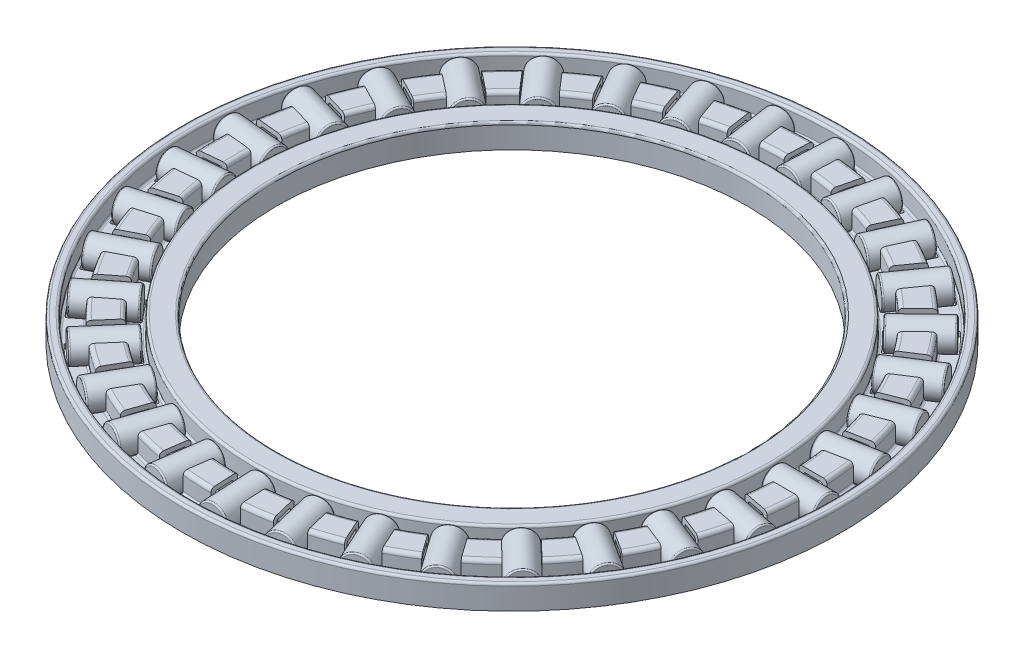
SolidWorks part; units mm, degrees
ref_plane "Front Plane" through (0, 0, 0) normal (0, 0, 1) x (1, 0, 0)
ref_plane "Top Plane" through (0, 0, 0) normal (0, 1, 0) x (1, 0, 0)
ref_plane "Right Plane" through (0, 0, 0) normal (1, 0, 0) x (0, 0, -1)
sketch "Sketch1" plane through (0, 0, 0) normal (1, 0, 0) x (0, 0, -1)
  line L0 (-35, 0) -> (35, 0) construction
  line L1 (-25.025, 0) -> (25.025, 0) construction
  line L2 (35, -1.5) -> (35, 1.5) construction
  line L3 (25.025, -1.275) -> (25.025, 1.275) construction
  line L4 (25.025, -1.275) -> (25.85, -1.275) construction
  line L5 (25.85, -1.275) -> (25.85, 0.7792) construction
  line L6 (25.85, 0.7792) -> (26.675, 0.7792) construction
  line L7 (26.675, 0.7792) -> (26.675, -1.275) construction
  line L8 (26.675, -1.275) -> (29.5042, -1.275) construction
  line L9 (29.5042, -1.275) -> (29.5042, 0.7792) construction
  line L10 (29.5042, 0.7792) -> (31.5042, 0.7792) construction
  line L11 (31.5042, 0.7792) -> (31.5042, -1.275) construction
  line L12 (31.5042, -1.275) -> (34.3333, -1.275) construction
  line L13 (34.3333, -1.275) -> (34.3333, 0.7792) construction
  line L14 (34.3333, 0.7792) -> (34.6667, 0.7792) construction
  line L15 (25.025, 1.275) -> (27.5, 1.275) construction
  line L16 (27.5, 1.275) -> (27.5, -0.7792) construction
  line L17 (27.5, -0.7792) -> (29.0083, -0.7792) construction
  line L18 (29.0083, -0.7792) -> (29.0083, 1.275) construction
  line L19 (29.0083, 1.275) -> (32, 1.275) construction
  line L20 (32, 1.275) -> (32, -0.7792) construction
  line L21 (32, -0.7792) -> (34, -0.7792) construction
  line L22 (34, -0.7792) -> (34, 1.275) construction
  line L23 (34, 1.275) -> (35, 1.275) construction
  line L24 (29.5042, 0.7792) -> (29.0083, 0.7792) construction
  line L25 (26.675, 0.7792) -> (26.675, 1.275) construction
  line L26 (31.5042, 0.7792) -> (32, 0.7792) construction
  line L27 (27.5, -0.7792) -> (27.5, -1.275) construction
  line L28 (27.5, -0.7792) -> (26.675, -0.7792) construction
  line L29 (34.3333, 0.7792) -> (34, 0.7792) construction
  line L30 (34.6667, 0.7792) -> (34.6667, -1.275) construction
  line L31 (34.6667, -1.275) -> (35, -1.275) construction
  line L32 (0, 1.5) -> (0, -1.5) construction
  line L33 (-27.5, 1.5) -> (27.5, 1.5) construction
  line L34 (-34, 1.275) -> (34, 1.275) construction
  line L35 (34.6667, 0.7792) -> (35, 0.7792) construction
  line L36 (29.0083, -0.7792) -> (29.0083, -1.275) construction
  line L37 (31.5042, 0.7792) -> (31.5042, 1.275) construction
  line L38 (25.85, -0.7792) -> (25.025, -0.7792) construction
  line L39 (26.675, -0.7792) -> (25.85, -0.7792) construction
  point P4 (0, 0)
  point P8 (0, 0)
  point P11 (35, 0)
  point P14 (25.025, 0)
  point P45 (0, 1.5)
  point P48 (0, 0)
  point P49 (0, 1.5)
  point P55 (0, 1.275)
  dimension "OD" = 70
  dimension "ID" = 50.05
  dimension "Thickness" = 3
  dimension "Approx. Raceway Thickness" = 2.55
  dimension "Inner Raceway" = 55
  dimension "Outer Raceway" = 68
  dimension "Approx. Raceway Notch Width" = 2
  dimension "D3" = 2
sketch "Sketch2" plane through (0, 0, 0) normal (0, 1, 0) x (1, 0, 0)
  line L0 (27.5, 0) -> (34, 0) construction
  line L1 (33.675, 0) -> (27.825, 0)
  line L2 (33.6416, -1.5) -> (27.7845, -1.5)
  line L3 (33.6416, 1.5) -> (27.7845, 1.5)
  circle A0 centre (0, 0) radius 25.025
  circle A1 centre (0, 0) radius 27.5
  circle A2 centre (0, 0) radius 34
  circle A3 centre (0, 0) radius 35
  arc A4 (27.7845, -1.5) -> (27.7845, 1.5) centre (0, 0) ccw
  arc A5 (33.6416, -1.5) -> (33.6416, 1.5) centre (0, 0) ccw
  arc A6 (33.6416, 1.5) -> (33.4133, 4.1905) centre (0, 0) ccw
  point P15 (30.75, 0)
  dimension "Approx. Roller Length" = 5.85
  dimension "Roller Thickness" = 3
  dimension "Roller Arc Length" = 3.001
  dimension "Approx. Roller Gap" = 2.7009
sketch "Sketch3" plane through (0, 0, 0) normal (1, 0, 0) x (0, 0, -1)
  line L0 (25.85, -1.275) -> (25.85, 0.7792)
  line L1 (25.85, 0.7792) -> (26.675, 0.7792)
  line L2 (26.675, 0.7792) -> (26.675, -1.275)
  line L3 (26.675, -1.275) -> (29.5042, -1.275)
  line L4 (29.5042, -1.275) -> (29.5042, 0.7792)
  line L5 (29.5042, 0.7792) -> (31.5042, 0.7792)
  line L6 (31.5042, 0.7792) -> (31.5042, -1.275)
  line L7 (31.5042, -1.275) -> (34.3333, -1.275)
  line L8 (34.3333, -1.275) -> (34.3333, 0.7792)
  line L9 (34.3333, 0.7792) -> (34.6667, 0.7792)
  line L10 (34.6667, 0.7792) -> (34.6667, -1.275)
  line L11 (34.6667, -1.275) -> (35, -1.275)
  line L12 (35, -1.275) -> (35, 1.275)
  line L13 (35, 1.275) -> (34, 1.275)
  line L14 (34, 1.275) -> (34, -0.7792)
  line L15 (34, -0.7792) -> (32, -0.7792)
  line L16 (32, -0.7792) -> (32, 1.275)
  line L17 (32, 1.275) -> (29.0083, 1.275)
  line L18 (29.0083, 1.275) -> (29.0083, -0.7792)
  line L19 (29.0083, -0.7792) -> (27.5, -0.7792)
  line L20 (27.5, -0.7792) -> (27.5, 1.275)
  line L21 (27.5, 1.275) -> (25.025, 1.275)
  line L22 (25.025, 1.275) -> (25.025, -1.275)
  line L23 (25.025, -1.275) -> (25.85, -1.275)
revolve "Revolve1" add sketch "Sketch3" angle 360 about L32
fillet "Fillet1" radius 0.4 4 edges at (0, -1.275, 31.5042) (0, -1.275, 34.3333) (0, -1.275, 26.675) (0, -1.275, 29.5042)
fillet "Fillet2" radius 0.4 2 edges at (0, 1.275, 32) (0, 1.275, 29.0083)
fillet "Fillet3" radius 0.25 4 edges at (0, 1.275, 34) (0, 1.275, 35) (0, 1.275, 27.5) (0, 1.275, 25.025)
fillet "Fillet4" radius 0.2 6 edges at (0, 0.7792, 29.5042) (0, 0.7792, 31.5042) (0, -0.7792, 34) (0, -0.7792, 32) (0, -0.7792, 29.0083) (0, -0.7792, 27.5)
sketch "Sketch4" plane through (0, 0, 0) normal (0, 1, 0) x (1, 0, 0)
  line L0 (27.7845, 1.5) -> (33.6416, 1.5)
  line L1 (27.7845, -1.5) -> (33.6416, -1.5)
  arc A0 (27.7845, -1.5) -> (27.7845, 1.5) centre (0, 0) ccw construction
  arc A1 (27.7845, -1.5) -> (27.7845, 1.5) centre (0, 0) ccw
  arc A2 (33.6416, -1.5) -> (33.6416, 1.5) centre (0, 0) ccw construction
  arc A3 (33.6416, -1.5) -> (33.6416, 1.5) centre (0, 0) ccw
extrude "Cut-Extrude1" cut sketch "Sketch4" against normal through all both and the other way through all
fillet "Fillet5" radius 0.15 4 edges at (33.6416, -1.0271, -1.5) (33.6416, -1.0271, 1.5) (27.7845, -1.0271, -1.5) (27.7845, -1.0271, 1.5)
pattern_circular "CirPattern1" count 33 over 360 about axis through (0, 1.5, 0) along (0, -1, 0) of "Cut-Extrude1", "Fillet5"
sketch "Sketch5" plane through (0, 0, 0) normal (0, 1, 0) x (1, 0, 0)
  line L0 (27.9425, 0) -> (27.9425, 1.5)
  line L2 (27.9425, 1.5) -> (33.4978, 1.5)
  line L3 (33.4978, 1.5) -> (33.4978, 0)
  line L4 (33.4978, 0) -> (27.9425, 0)
  line L5 (33.675, 0) -> (27.825, 0) construction
revolve "Revolve2" add sketch "Sketch5" angle 360 about L1
fillet "Fillet6" radius 0.15 2 edges at (27.9425, 0, -1.5) (33.4978, 0, -1.5)
pattern_circular "CirPattern2" count 33 over 360 about axis through (0, 1.5, 0) along (0, -1, 0) of bodies 107
ref_axis "Center Axis 1" through (0, 1.65, 0) along (0, -1, 0)
ref_plane "Contact Plane 1" through (0, 1.5, 0) normal (0, 1, 0) x (1, 0, 0)
ref_plane "Contact Plane 2" through (0, -1.5, 0) normal (0, 1, 0) x (1, 0, 0)
ref_plane "Plane1" through (0, 1.5, 0) normal (0, 1, 0) x (1, 0, 0)
ref_plane "Plane2" through (0, -1.5, 0) normal (0, 1, 0) x (1, 0, 0)
equation "\"Approx. Raceway Thickness@Sketch1\" = \"Thickness@Sketch1\" * .85"
equation "\"Approx. Raceway Notch Width@Sketch1\" =  ( \"Outer Raceway@Sketch1\" - \"Inner Raceway@Sketch1\" )  / 6.5"
equation "\"D3@Sketch1\" = \"Approx. Raceway Notch Width@Sketch1\""
equation "\"D1@Fillet2\"=\"D1@Fillet1\""
equation "\"D1@Fillet3\"=(\"OD@Sketch1\"-\"Outer Raceway@Sketch1\")/8"
equation "\"D1@Fillet1\" = \"Approx. Raceway Notch Width@Sketch1\" * 2 / 10"
equation "\"D1@Fillet4\"=\"D1@Fillet2\"/2"
equation "\"Approx. Roller Length@Sketch2\" =  ( \"Outer Raceway@Sketch1\" - \"Inner Raceway@Sketch1\" )  / 2 * .9"
equation "\"Approx. Roller Gap@Sketch2\" = \"Roller Arc Length@Sketch2\" * .9"
equation "\"Raceway Diff\"= ( \"Outer Raceway@Sketch1\" - \"Inner Raceway@Sketch1\" )"
equation "\"Circumference\"= ( \"Inner Raceway@Sketch1\" + ( \"Raceway Diff\" / 2 ) ) * 3.14"
equation "\"Instances\"= int ( \"Circumference\" /  ( \"Roller Arc Length@Sketch2\" + \"Approx. Roller Gap@Sketch2\" )  ) "
equation "\"D1@CirPattern1\"=\"Instances\""
equation "\"D1@Fillet5\" = \"Roller Arc Length@Sketch2\" / 20"
equation "\"D1@Fillet6\" = \"Roller Arc Length@Sketch2\" / 20"
equation "\"D1@CirPattern2\" = \"D1@CirPattern1\""
equation "\"Roller Thickness@Sketch2\" = \"Thickness@Sketch1\""
